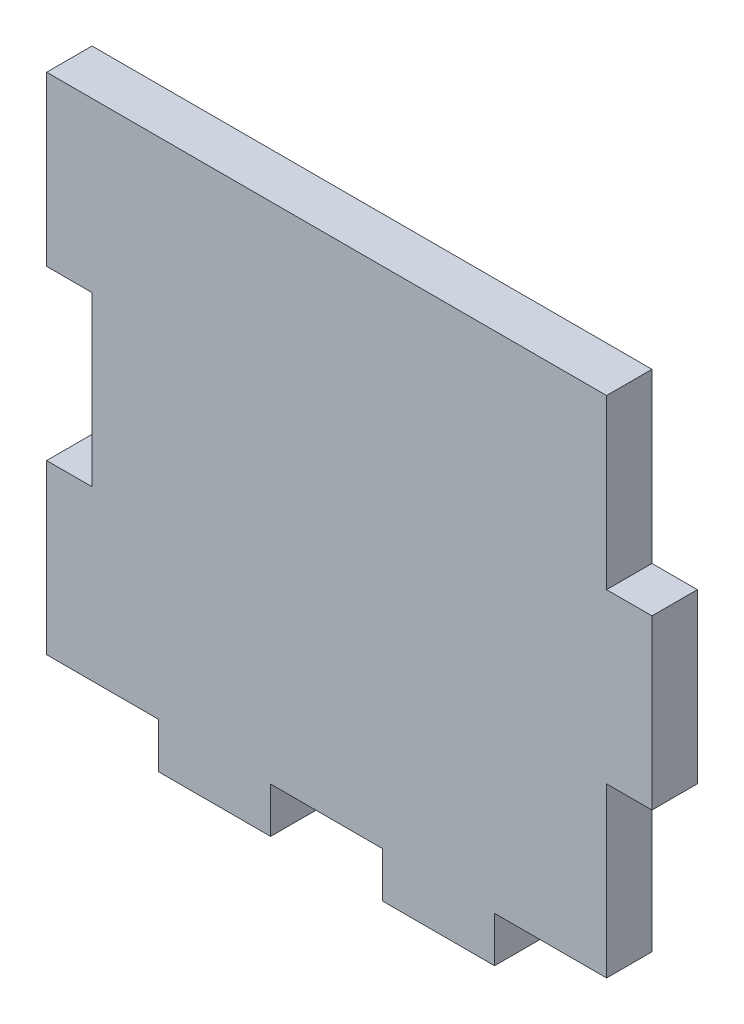
SolidWorks part; units mm, degrees
ref_plane "Front Plane" through (0, 0, 0) normal (0, 0, 1) x (1, 0, 0)
ref_plane "Top Plane" through (0, 0, 0) normal (0, 1, 0) x (1, 0, 0)
ref_plane "Right Plane" through (0, 0, 0) normal (1, 0, 0) x (0, 0, -1)
sketch "Sketch1" plane through (0, 0, 0) normal (0, 0, 1) x (1, 0, 0)
  line L0 (22.2, 0) -> (33.3, 0)
  line L1 (0, 0) -> (11.1, 0)
  line L2 (0, 0) -> (0, 16.6667)
  line L3 (0, 50) -> (20, 50)
  line L4 (55.5, 0) -> (55.5, 16.6667)
  line L5 (44.4, 0) -> (55.5, 0)
  line L6 (11.1, 0) -> (11.1, -4.5)
  line L7 (11.1, -4.5) -> (22.2, -4.5)
  line L8 (22.2, 0) -> (22.2, -4.5)
  line L9 (0, 33.3333) -> (0, 50)
  line L10 (33.3, 0) -> (33.3, -4.5)
  line L11 (33.3, -4.5) -> (44.4, -4.5)
  line L12 (44.4, 0) -> (44.4, -4.5)
  line L13 (55.5, 16.6667) -> (60, 16.6667)
  line L14 (40, 50) -> (55.5, 50)
  line L15 (55.5, 33.3333) -> (60, 33.3333)
  line L16 (60, 16.6667) -> (60, 33.3333)
  line L17 (0, 33.3333) -> (4.5, 33.3333)
  line L18 (55.5, 33.3333) -> (55.5, 50)
  line L19 (0, 16.6667) -> (4.5, 16.6667)
  line L20 (4.5, 33.3333) -> (4.5, 16.6667)
  line L21 (60, 50) -> (40, 50) construction
  line L22 (20, 50) -> (40, 50)
  line L25 (60, 39.1343) -> (60, 50039.1343) construction
  dimension "D1" = 4.5
  dimension "D2" = 60
  dimension "D3" = 50
extrude "Boss-Extrude1" add sketch "Sketch1" along normal blind 4.5
equation "\"D1@Sketch1\" = \"mat@v5.assembly\""
equation "\"D1@Boss-Extrude1\"=\"mat@v5.assembly\""
